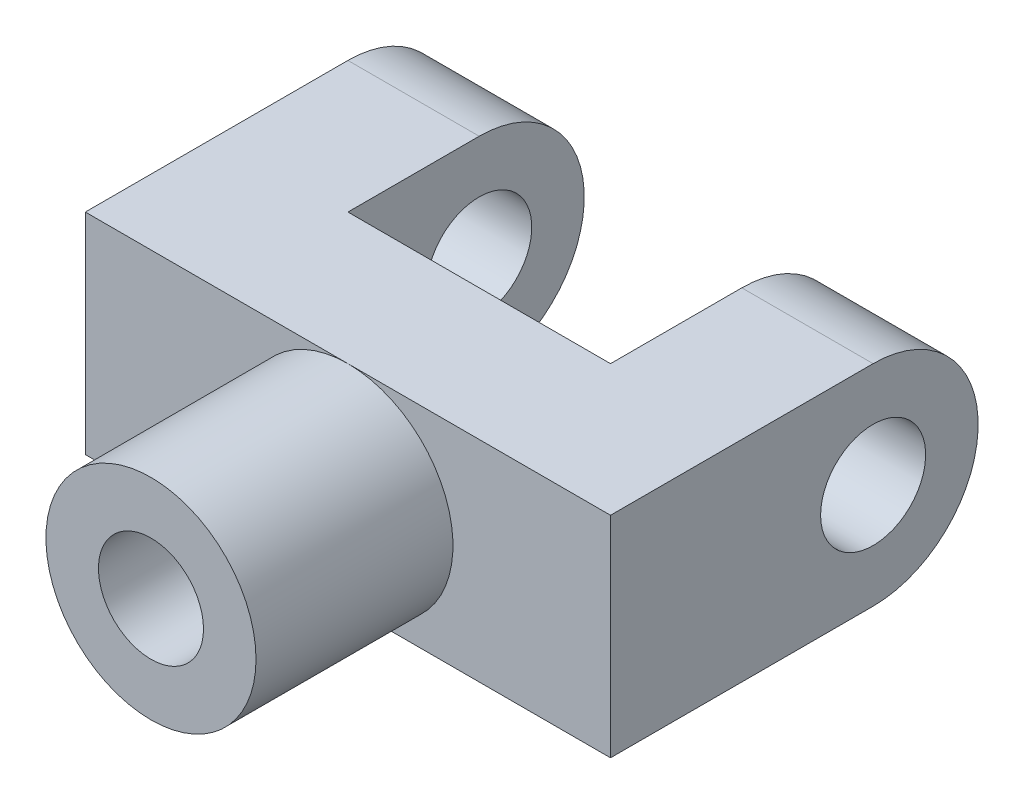
SolidWorks part; units mm, degrees
ref_plane "Front Plane" through (0, 0, 0) normal (0, 0, 1) x (1, 0, 0)
ref_plane "Top Plane" through (0, 0, 0) normal (0, 1, 0) x (1, 0, 0)
ref_plane "Right Plane" through (0, 0, 0) normal (1, 0, 0) x (0, 0, -1)
sketch "Sketch1" plane through (0, 0, 0) normal (0, 0, 1) x (1, 0, 0)
  line L1 (-10, 4) -> (10, 4)
  line L2 (-10, 4) -> (-10, -4)
  line L3 (-10, -4) -> (10, -4)
  line L4 (10, 4) -> (10, -4)
  line L5 (-10, 4) -> (10, -4) construction
  line L6 (-10, -4) -> (10, 4) construction
  circle A0 centre (0, 0) radius 4
  circle A1 centre (0, 0) radius 2
  point P0 (0, 0)
  dimension "D3" = 4
  dimension "D1" = 8
  dimension "D2" = 20
extrude "Boss-Extrude1" add sketch "Sketch1" along normal mid plane 5 contours A0 L3 L4 L1 | A0 L1 L2 L3 | A0 A1 | A1 region at (-6.5127, 0, 0) region at (6.5127, 0, 0) region at (2.7484, 2.7484, 0) region at (0, 0, 0)
extrude "Boss-Extrude2" add sketch "Sketch1<3>" along normal blind 10 contours A0 A1 region at (2.7484, 2.7484, 0)
sketch "Sketch1<3>" plane through (0, 0, 0) normal (0, 0, 1) x (1, 0, 0) same geometry as "Sketch1"
sketch "Sketch2" plane through (-10, 0, 0) normal (-1, 0, 0) x (0, 0, 1)
  line L1 (-2.5, 4) -> (-7.5, 4)
  line L2 (-2.5, 4) -> (-2.5, -4)
  line L3 (-2.5, -4) -> (-7.5, -4)
  line L4 (-7.5, 4) -> (-7.5, -4)
  circle A0 centre (-7.5, 0) radius 4
  circle A1 centre (-7.5, 0) radius 2
  line M7 (-2.5, 4) -> (-2.5, -4)
  dimension "D2" = 4
  dimension "D1" = 5
extrude "Boss-Extrude3" add sketch "Sketch2" against normal blind 5 contours A0 L3 L1 M7 | A1 L4 A0 | A1 L4 A0 region at (-10, 0, -2.5943) region at (-10, 2.7652, -4.7348) region at (-10, 3, -7.5894)
mirror "Mirror1" about plane through (0, 0, 0) normal (1, 0, 0) of "Boss-Extrude3"
